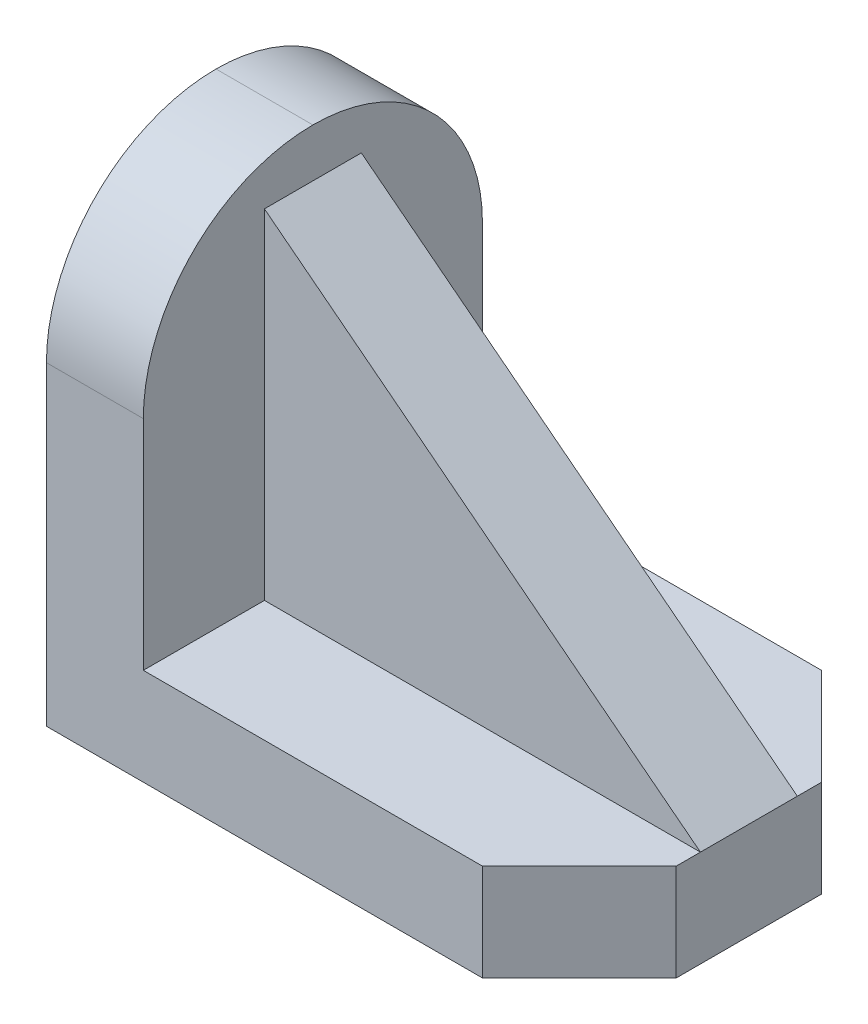
SolidWorks part; units mm, degrees
ref_plane "Front Plane" through (0, 0, 0) normal (0, 0, 1) x (1, 0, 0)
ref_plane "Top Plane" through (0, 0, 0) normal (0, 1, 0) x (1, 0, 0)
ref_plane "Right Plane" through (0, 0, 0) normal (1, 0, 0) x (0, 0, -1)
sketch "Sketch1" plane through (0, 0, 0) normal (0, 1, 0) x (1, 0, 0)
  line L0 (0, 0) -> (137.16, 0)
  line L1 (137.16, 0) -> (167.64, 30.48)
  line L2 (167.64, 30.48) -> (167.64, 76.2)
  line L3 (167.64, 76.2) -> (137.16, 106.68)
  line L4 (137.16, 106.68) -> (0, 106.68)
  line L5 (0, 106.68) -> (0, 0)
  line L6 (137.16, 106.68) -> (137.16, 0) construction
  dimension "D1" = 135
  dimension "D2" = 135
  dimension "D3" = 45.72
  dimension "D4" = 106.68
  dimension "D5" = 137.16
extrude "Boss-Extrude1" add sketch "Sketch1" along normal blind 30.48
sketch "Sketch2" plane through (0, 30.48, 0) normal (0, 1, 0) x (1, 0, 0)
  line L0 (0, 106.68) -> (0, 0)
  line L1 (0, 0) -> (30.48, 0)
  line L2 (0, 0) -> (137.16, 0) construction
  line L3 (30.48, 0) -> (30.48, 106.68)
  line L4 (137.16, 106.68) -> (0, 106.68) construction
  line L5 (30.48, 106.68) -> (0, 106.68)
  line L6 (167.64, 30.48) -> (167.64, 76.2) construction
  line L7 (30.48, 38.1) -> (167.64, 38.1)
  line L8 (30.48, 38.1) -> (30.48, 68.58)
  line L9 (30.48, 68.58) -> (167.64, 68.58)
  line L10 (167.64, 38.1) -> (167.64, 68.58)
  line M4 (0, 106.68) -> (0, 0)
  line M5 (0, 0) -> (137.16, 0)
  line M7 (167.64, 30.48) -> (167.64, 76.2)
  line M9 (137.16, 106.68) -> (0, 106.68)
  dimension "D1" = 30.48
  dimension "D2" = 38.1
  dimension "D3" = 30.48
extrude "Boss-Extrude2" add sketch "Sketch2" along normal blind 121.92 contours L3 M5 M9 M4 region at (15.24, 30.48, -53.34)
extrude "Boss-Extrude3" add sketch "Sketch2<3>" along normal blind 106.68 contours L9 L3 L7 M7 region at (99.06, 30.48, -53.34)
sketch "Sketch2<3>" plane through (0, 30.48, 0) normal (0, 1, 0) x (1, 0, 0) same geometry as "Sketch2"
fillet "Fillet1" radius 53.34 2 edges at (15.24, 152.4, -106.68) (15.24, 152.4, 0)
chamfer "Chamfer1" distance 106.68 distance2 137.16 1 edges at (167.64, 137.16, -53.34) first distance on face at (167.64, 49.53, -53.34)
